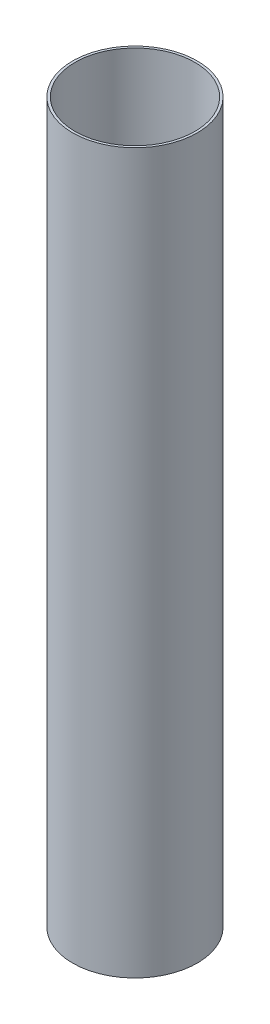
SolidWorks part; units mm, degrees
material "S-Glass Fiber"
ref_plane "Front Plane" through (0, 0, 0) normal (0, 0, 1) x (1, 0, 0)
ref_plane "Top Plane" through (0, 0, 0) normal (0, 1, 0) x (1, 0, 0)
ref_plane "Right Plane" through (0, 0, 0) normal (1, 0, 0) x (0, 0, -1)
sketch "Sketch1" plane through (0, 0, 0) normal (0, 1, 0) x (1, 0, 0)
  circle A0 centre (0, 0) radius 39.624
  circle A1 centre (0, 0) radius 38.1
  dimension "D1" = 79.248
  dimension "D2" = 76.2
extrude "Boss-Extrude1" add sketch "Sketch1" along normal blind 457.2 contours A1 | A0
